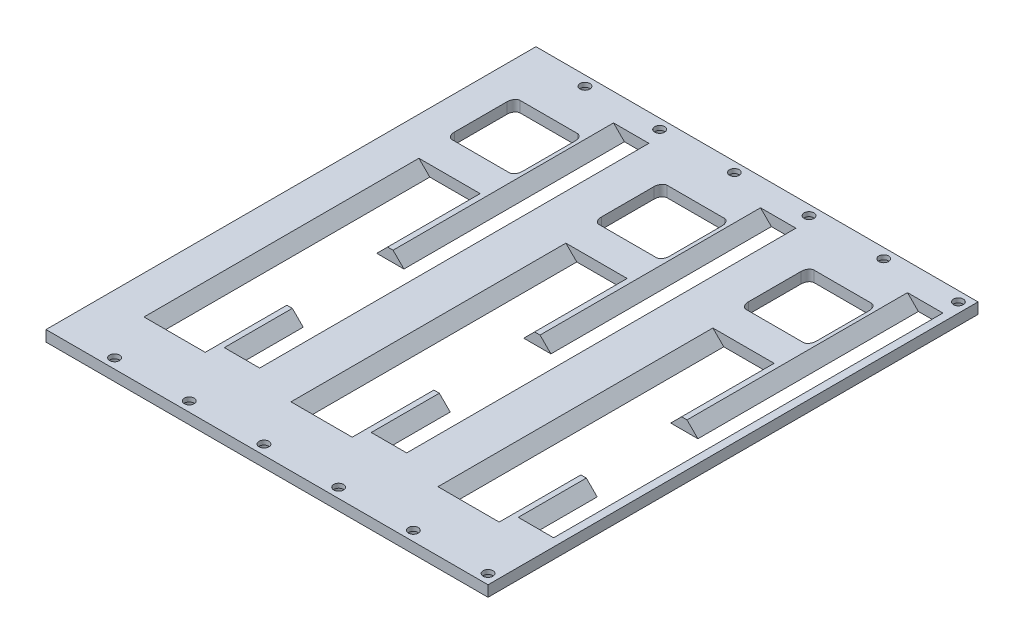
SolidWorks part; units mm, degrees
ref_plane "Płaszczyzna przednia" through (0, 0, 0) normal (0, 0, 1) x (1, 0, 0)
ref_plane "Płaszczyzna górna" through (0, 0, 0) normal (0, 1, 0) x (1, 0, 0)
ref_plane "Płaszczyzna prawa" through (0, 0, 0) normal (1, 0, 0) x (0, 0, -1)
sketch "Szkic1" plane through (0, 0, 0) normal (0, 1, 0) x (1, 0, 0)
  line L1 (-81.2, -90) -> (81.2, -90)
  line L2 (-81.2, -90) -> (-81.2, 90)
  line L3 (-81.2, 90) -> (81.2, 90)
  line L4 (81.2, -90) -> (81.2, 90)
  line L5 (0, 90) -> (0, -90) construction
  line L6 (-81.2, 0) -> (81.2, 0) construction
  point P0 (0, 0)
  dimension "D1" = 162.4
  dimension "D2" = 180
extrude "Dodanie-wyciągnięcie1" add sketch "Szkic1" along normal blind 4
sketch "Szkic2" plane through (0, 0, 0) normal (0, -1, 0) x (1, 0, 0)
  line L0 (-44, -47.8284) -> (-44, -67.1716) construction
  line L1 (-46, -70) -> (-67, -70) construction
  line L2 (-69, -67.1716) -> (-69, -47.8284) construction
  line L3 (-67, -45) -> (-46, -45) construction
  line L4 (-44, -47.8284) -> (-44, -67.1716)
  line L5 (-46, -70) -> (-67, -70)
  line L6 (-69, -67.1716) -> (-69, -47.8284)
  line L7 (-67, -45) -> (-46, -45)
  line L8 (81.2, -130) -> (-81.2, -130) construction
  line L9 (10, -47.8284) -> (10, -67.1716)
  line L10 (8, -70) -> (-13, -70)
  line L11 (-15, -67.1716) -> (-15, -47.8284)
  line L12 (-81.2, 90) -> (81.2, 90) construction
  line L13 (-81.2, -130) -> (-81.2, 90) construction
  line L15 (-13, -45) -> (8, -45)
  line L16 (-9.2, -33) -> (5.3, -33)
  line L17 (5.3, -33) -> (5.3, 1)
  line L18 (5.3, 1) -> (15.3, 1)
  line L19 (15.3, 1) -> (15.3, -80)
  line L20 (15.3, -80) -> (20.3, -80)
  line L21 (20.3, -80) -> (20.3, 63)
  line L22 (20.3, 63) -> (15.3, 63)
  line L23 (15.3, 63) -> (15.3, 38)
  line L24 (-63.2, -33) -> (-48.7, -33)
  line L25 (-48.7, -33) -> (-48.7, 1)
  line L26 (-48.7, 1) -> (-38.7, 1)
  line L27 (-38.7, 1) -> (-38.7, -80)
  line L28 (-38.7, -80) -> (-33.7, -80)
  line L29 (-33.7, -80) -> (-33.7, 63)
  line L30 (-33.7, 63) -> (-38.7, 63)
  line L31 (-38.7, 63) -> (-38.7, 38)
  line L32 (-38.7, 38) -> (-48.7, 38)
  line L33 (-48.7, 38) -> (-48.7, 68)
  line L34 (-48.7, 68) -> (-63.2, 68)
  line L35 (-63.2, 68) -> (-63.2, -33)
  line L36 (15.3, 38) -> (5.3, 38)
  line L37 (5.3, 38) -> (5.3, 68)
  line L38 (5.3, 68) -> (-9.2, 68)
  line L39 (-9.2, 68) -> (-9.2, -33)
  line L40 (64, -47.8284) -> (64, -67.1716)
  line L41 (62, -70) -> (41, -70)
  line L42 (39, -67.1716) -> (39, -47.8284)
  line L43 (41, -45) -> (62, -45)
  line L44 (44.8, -33) -> (59.3, -33)
  line L45 (59.3, -33) -> (59.3, 1)
  line L46 (59.3, 1) -> (69.3, 1)
  line L47 (69.3, 1) -> (69.3, -80)
  line L48 (69.3, -80) -> (74.3, -80)
  line L49 (74.3, -80) -> (74.3, 63)
  line L50 (74.3, 63) -> (69.3, 63)
  line L51 (69.3, 63) -> (69.3, 38)
  line L52 (69.3, 38) -> (59.3, 38)
  line L53 (59.3, 38) -> (59.3, 68)
  line L54 (59.3, 68) -> (44.8, 68)
  line L55 (44.8, 68) -> (44.8, -33)
  ellipse E0 centre (-46, -47.8284) end of major axis (-46, -45) minor radius 2 (-44, -47.8284) -> (-46, -45) ccw construction
  ellipse E1 centre (-46, -67.1716) end of major axis (-46, -64.3431) minor radius 2 (-46, -70) -> (-44, -67.1716) ccw construction
  ellipse E2 centre (-67, -67.1716) end of major axis (-67, -64.3431) minor radius 2 (-69, -67.1716) -> (-67, -70) ccw construction
  ellipse E3 centre (-67, -47.8284) end of major axis (-67, -45) minor radius 2 (-67, -45) -> (-69, -47.8284) ccw construction
  ellipse E4 centre (-46, -47.8284) end of major axis (-46, -45) minor radius 2 (-44, -47.8284) -> (-46, -45) ccw
  ellipse E5 centre (-46, -67.1716) end of major axis (-46, -64.3431) minor radius 2 (-46, -70) -> (-44, -67.1716) ccw
  ellipse E6 centre (-67, -67.1716) end of major axis (-67, -64.3431) minor radius 2 (-69, -67.1716) -> (-67, -70) ccw
  ellipse E7 centre (-67, -47.8284) end of major axis (-67, -45) minor radius 2 (-67, -45) -> (-69, -47.8284) ccw
  ellipse E8 centre (8, -47.8284) end of major axis (8, -45) minor radius 2 (10, -47.8284) -> (8, -45) ccw
  ellipse E9 centre (8, -67.1716) end of major axis (8, -64.3431) minor radius 2 (8, -70) -> (10, -67.1716) ccw
  ellipse E10 centre (-13, -67.1716) end of major axis (-13, -64.3431) minor radius 2 (-15, -67.1716) -> (-13, -70) ccw
  ellipse E11 centre (-13, -47.8284) end of major axis (-13, -45) minor radius 2 (-13, -45) -> (-15, -47.8284) ccw
  ellipse E12 centre (62, -47.8284) end of major axis (62, -45) minor radius 2 (64, -47.8284) -> (62, -45) ccw
  ellipse E13 centre (62, -67.1716) end of major axis (62, -64.3431) minor radius 2 (62, -70) -> (64, -67.1716) ccw
  ellipse E14 centre (41, -67.1716) end of major axis (41, -64.3431) minor radius 2 (39, -67.1716) -> (41, -70) ccw
  ellipse E15 centre (41, -47.8284) end of major axis (41, -45) minor radius 2 (41, -45) -> (39, -47.8284) ccw
  dimension "D1" = 22
  dimension "D2" = 14.5
  dimension "D3" = 18
  dimension "D4" = 10
  dimension "D5" = 5
  dimension "D6" = 5
  dimension "D7" = 25
  dimension "D8" = 37
  dimension "D9" = 97
  dimension "D10" = 47
  dimension "D12" = 54
  dimension "D11" = 3
extrude "Wytnij-wyciągnięcie1" cut sketch "Szkic2" against normal up to next
chamfer "Sfazowanie1" distance 4 angle 45 18 edges at (69.3, 4, -39.5) (74.3, 4, -8.5) (69.3, 4, 50.5) (59.3, 4, 53) (59.3, 4, -16) (44.8, 4, 17.5) (15.3, 4, -39.5) (15.3, 4, 50.5) (20.3, 4, -8.5) (5.3, 4, 53) (5.3, 4, -16) (-9.2, 4, 17.5) (-33.7, 4, -8.5) (-38.7, 4, -39.5) (-38.7, 4, 50.5) (-48.7, 4, 53) (-48.7, 4, -16) (-63.2, 4, 17.5)
sketch "Szkic3" plane through (0, 0, 0) normal (0, -1, 0) x (1, 0, 0)
  line L0 (81.2, 90) -> (81.2, -90) construction
  line L1 (81.2, -90) -> (-81.2, -90) construction
  line L2 (0, 0) -> (-81.2, 0) construction
  line L3 (-81.2, -90) -> (-81.2, 90) construction
  point P1 (77.6, -86.4)
  point P6 (50.16, -86.4)
  point P8 (22.72, -86.4)
  point P9 (-4.72, -86.4)
  point P10 (-32.16, -86.4)
  point P11 (-59.6, -86.4)
  point P15 (-59.6, 86.4)
  point P16 (-32.16, 86.4)
  point P17 (-4.72, 86.4)
  point P18 (22.72, 86.4)
  point P19 (50.16, 86.4)
  point P20 (77.6, 86.4)
  dimension "D1" = 3.6
  dimension "D2" = 3.6
  dimension "D4" = 27.44
  dimension "D3" = 6
hole_wizard "Pogłębienie walcowe pod M3 Śrubę z łbem stożkowym ściętym1" positions "Szkic3" profile "Szkic4" counterbore size "M3" standard "DIN"
sketch "Szkic4" plane through (77.6, 0, 86.4) normal (1, 0, 0) x (0, 0, -1)
  line L0 (0, 0) -> (0, 7.7815)
  line L1 (0, 7.7815) -> (1.8, 6.7)
  line L2 (1.8, 6.7) -> (1.8, 2.4)
  line L3 (1.8, 2.4) -> (3.5, 2.4)
  line L4 (3.5, 2.4) -> (3.5, 0)
  line L5 (3.5, 0) -> (0, 0)
  line L10 (0, 7.7815) -> (-1.8, 6.7) construction
  line L11 (0, -6.35) -> (0, 107.95) construction
  dimension "Średnica otworu" = 3.6
  dimension "Głębokość otworu" = 6.7
  dimension "Średnica pogłębienia walcowego" = 7
  dimension "Głębokość pogłębienia walcowego" = 2.4
  dimension "Kąt wiertła" = 118
